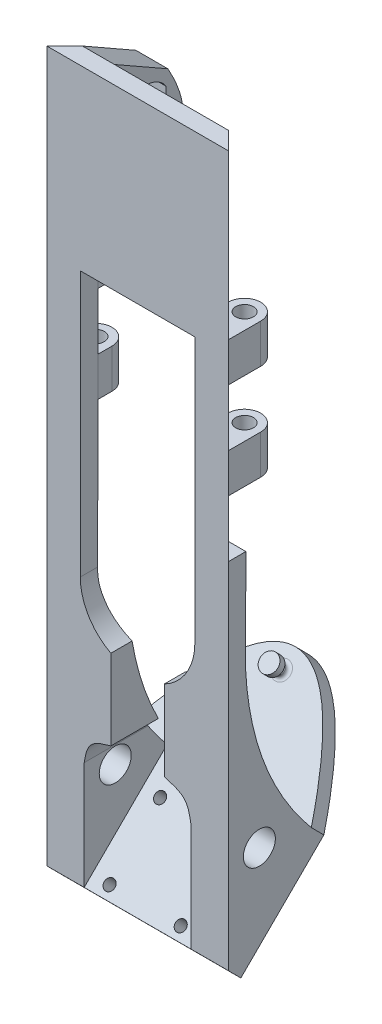
SolidWorks part; units mm, degrees
ref_plane "Front Plane" through (0, 0, 0) normal (0, 0, 1) x (1, 0, 0)
ref_plane "Top Plane" through (0, 0, 0) normal (0, 1, 0) x (1, 0, 0)
ref_plane "Right Plane" through (0, 0, 0) normal (1, 0, 0) x (0, 0, -1)
sketch "Sketch1" plane through (0, 0, 0) normal (0, 1, 0) x (1, 0, 0)
  line L0 (-25.5, 5) -> (-25.5, 9.1071)
  line L1 (25.5, 0) -> (-25.5, 0)
  line L2 (0, 0) -> (0, 5) construction
  line L3 (16.3088, 5) -> (-16.3088, 5)
  line L4 (-25.5, 0) -> (-25.5, 5)
  line L5 (-16.3088, 9.1071) -> (-16.3088, 5)
  line L6 (-16.3088, 5) -> (-25.5, 5) construction
  line L7 (16.3088, 9.1071) -> (16.3088, 5)
  line L8 (25.5, 5) -> (25.5, 9.1071)
  line L9 (25.5, 0) -> (25.5, 5)
  circle A1 centre (-20.9604, 9.1071) radius 2.5
  arc A3 (-25.5, 9.1071) -> (-16.3088, 9.1071) centre (-20.9044, 9.1071) cw
  circle A4 centre (20.9604, 9.1071) radius 2.5
  arc A5 (25.5, 9.1071) -> (16.3088, 9.1071) centre (20.9044, 9.1071) ccw
  dimension "D2" = 5
  dimension "D3" = 5
  dimension "D4" = 4.5956
  dimension "D1" = 25.5
extrude "Boss-Extrude1" add sketch "Sketch1" along normal blind 200
sketch "Sketch4" plane through (25.5, 0, 0) normal (1, 0, 0) x (0, 0, -1)
  line L1 (5, 170) -> (13.7027, 170)
  line L2 (5, 170) -> (5, 154)
  line L3 (5, 154) -> (13.7027, 154)
  line L4 (13.7027, 170) -> (13.7027, 154)
  line L5 (0, 200) -> (0, 0) construction
  line L6 (13.7027, 0) -> (13.7027, 200) construction
  line L15 (5, 143) -> (13.7027, 143)
  line L16 (5, 143) -> (5, 127)
  line L17 (5, 127) -> (13.7027, 127)
  line L18 (13.7027, 143) -> (13.7027, 127)
  line L19 (5, 116) -> (13.7027, 116)
  line L23 (5, 100) -> (13.7027, 100) [skipped]
  line L24 (13.7027, 116) -> (13.7027, 100) [skipped]
  line L25 (5, 116) -> (5, 100) [skipped]
  line L26 (5, 116) -> (4.5536, 0)
  line L27 (0, 0) -> (9.1071, 0) construction
  line L28 (4.5536, 0) -> (13.7027, 0)
  line L29 (9.1071, 0) -> (13.7027, 0) construction
  line L30 (13.7027, 0) -> (13.7027, 116)
  line L31 (5, 170) -> (5, 200)
  line L32 (0, 200) -> (9.1071, 200) construction
  line L33 (5, 200) -> (13.7027, 200)
  line L34 (13.7027, 170) -> (13.7027, 200)
  line M4 (0, 0) -> (9.1071, 0)
  line M5 (9.1071, 0) -> (9.1071, 200)
  line M6 (9.1071, 200) -> (0, 200)
  dimension "D1" = 16
  dimension "D2" = 5
  dimension "D4" = 116
  dimension "D5" = 11
  dimension "D6" = 11
  dimension "D3" = 3
extrude "Cut-Extrude4" cut sketch "Sketch4" against normal through all contours L1 L34 L33 M5 | L31 L1 M5 M6 | L2 L3 L1 M5 | L4 L1 L3 M5 | L16 L17 L15 M5 | L18 L15 L17 M5 | L19 L26 M4 M5 | L28 L30 L19 M5 region at (25.5, 185, -7.0536) region at (25.5, 162, -7.0536) region at (25.5, 108, -11.4049) region at (25.5, 108, -7.0536) region at (25.5, 135, -11.4049) region at (25.5, 135, -7.0536) region at (25.5, 185, -11.4049) region at (25.5, 162, -11.4049) region at (25.5, 49.3279, -6.923) region at (25.5, 50, -11.4049)
chamfer "Chamfer2" distance 5 angle 45 1 edges at (0, 0, -4.5536) first distance on face at (0, 77.3333, -4.8512)
sketch "Sketch7" plane through (-25.5, 0, 0) normal (-1, 0, 0) x (0, 0, 1)
  line L0 (-4.5728, 5) -> (-23.3302, 23.6135)
  line L2 (-5, 116) -> (-4.5728, 5) construction
  line L3 (-4.83, 71.8196) -> (-4.5728, 5)
  line L5 (-4.5728, 5) -> (0, 0.4622) construction
  spline S0 degree 2 poles (-23.3302, 23.6135) (-6.1606, 44.077) (-4.83, 71.8196) knots 0 0 0 1 1 1
extrude "Boss-Extrude2" add sketch "Sketch7" against normal through all
sketch "Sketch5" plane through (0, 0, 0) normal (0, 0, 1) x (1, 0, 0)
  line L0 (-16.0968, 75.4622) -> (-16.0968, 150)
  line L1 (-15, 38.66) -> (-7.5, 38.66) construction
  line L2 (-15, 30.832) -> (-15, 0)
  line L3 (-15, 0) -> (15, 0)
  line L4 (15, 30.832) -> (15, 0)
  line L6 (-25.5, 0.4622) -> (25.5, 0.4622) construction
  line L7 (-7.5, 75.4622) -> (7.5, 75.4622)
  line L8 (-7.5, 75.4622) -> (-7.5, 38.66)
  line L9 (-7.5, 38.66) -> (7.5, 38.66) construction
  line L10 (7.5, 75.4622) -> (7.5, 38.66)
  line L11 (-16.0968, 150) -> (16.0968, 150)
  line L12 (16.0968, 150) -> (16.0968, 75.4622)
  line L13 (-7.5, 38.66) -> (7.5, 38.66) construction
  line L14 (7.5, 38.66) -> (15, 38.66) construction
  line L15 (-15, 38.66) -> (-15, 30.832) construction
  line L16 (0, 0) -> (0, 83.4591) construction
  line L17 (15, 38.66) -> (15, 30.832) construction
  line L18 (-25.5, 200) -> (25.5, 200) construction
  circle A0 centre (0, 75.4622) radius 16.0968
  spline S0 degree 3 poles (-7.5, 38.66) (-9.7956, 38.0172) (-13.9471, 36.8549) (-14.6747, 32.6926) (-15, 30.832) knots 0 0 0 0 0.552974 1 1 1 1
  spline S1 degree 3 poles (7.5, 38.66) (9.7956, 38.0172) (13.9471, 36.8549) (14.6747, 32.6926) (15, 30.832) knots 0 0 0 0 0.552974 1 1 1 1
  point P4 (0, 0)
  line M7 (-25.5, 0.4622) -> (25.5, 0.4622)
  line M9 (25.5, 200) -> (-25.5, 200)
  dimension "D1" = 30
  dimension "D2" = 15
  dimension "D3" = 75
  dimension "D4" = 50
extrude "Cut-Extrude5" cut sketch "Sketch5" against normal through all contours L10 A0 L8 L7 | L8 A0 L10 L7 | A0 L8 L1 L10 | L4 L1 L2 M7 | A0 L12 L0 M9 region at (0, 118.9481, 0) region at (0, 78.5617, 0) region at (0, 25.8407, 0) region at (0, 67.7056, 0)
sketch "Sketch8" plane through (-25.5, 0, 0) normal (-1, 0, 0) x (0, 0, 1)
  line L1 (-23.3302, 23.6135) -> (0, 0.4622) construction
  circle A0 centre (-8.7271, 26.028) radius 4.5
  dimension "D1" = 9
  dimension "D2" = 12
extrude "Cut-Extrude6" cut sketch "Sketch8" against normal through all
sketch "Sketch9" plane through (0, 0.2329, 0.2311) normal (0, -0.7098, -0.7044) x (1, 0, 0)
  line L0 (-25.5, -0.3256) -> (-25.5, -33.1931)
  line L1 (-25.5, -0.3256) -> (25.5, -0.3256)
  line L5 (25.5, -0.3256) -> (25.5, -33.1931)
  spline S0 degree 2 poles (-25.5, -33.1931) (0, -92.2955) (25.5, -33.1931) knots 0 0 0 1 1 1
extrude "Boss-Extrude3" add sketch "Sketch9" along normal blind 5
sketch "Sketch10" plane through (0, 0.2329, 0.2311) normal (0, 0.7098, 0.7044) x (1, 0, 0)
  line L0 (0, 57.3395) -> (0, -1.5639) construction
  line L1 (0, 33.1931) -> (25.5, 33.1931) construction
  line L2 (-15, 33.1931) -> (-25.5, 33.1931) construction
  line L3 (-7.334, 27.3395) -> (0, 27.3395) construction
  line L4 (0, 27.3395) -> (10.7318, 27.3395) construction
  line L5 (-25.5, 33.1931) -> (0, 33.1931) construction
  circle A0 centre (0, 57.3395) radius 1.5
  parabola Q0 (-25.5, 33.1931) -> (25.5, 33.1931) focus (0, 57.2433) apex (0, 62.7443) construction
  dimension "D1" = 3
  dimension "D2" = 30
  dimension "D3" = 57.3395
extrude "Boss-Extrude4" add sketch "Sketch10" along normal blind 16 from offset 13 offset against normal yes
chamfer "Chamfer11" distance 5 angle 45 4 edges at (25.5, 135, -5) (25.5, 177, -5) (-25.5, 135, -5) (-25.5, 177, -5)
sketch "Sketch11" plane through (0, 2.3624, 2.3442) normal (0, 0.7098, 0.7044) x (1, 0, 0)
  circle A2 centre (0, 57.3395) radius 2.5
  circle A3 centre (0, 57.3395) radius 2.5
  dimension "D1" = 1
extrude "Boss-Extrude5" add sketch "Sketch11" along normal blind 2
fillet "Fillet1" radius 1 2 edges at (0, 39.5651, -39.405) (0, 41.6946, -37.2919)
sketch "Sketch13" plane through (-25.5, 0, 0) normal (-1, 0, 0) x (0, 0, 1)
  line L0 (-5, 200) -> (-5, 171)
  line L1 (-5, 154) -> (-5, 200) construction
  line L2 (-20.0185, 191.4487) -> (-5, 200)
  line L3 (-19.5, 187.4641) -> (-19.5, 180.5359)
  line L4 (-19.5, 187.4641) -> (-19.5, 180.5359) construction
  line L5 (-8.5, 187.4641) -> (-8.5, 180.5359)
  arc A0 (-8.5, 187.4641) -> (-19.5, 187.4641) centre (-14, 184) ccw
  arc A1 (-8.5, 180.5359) -> (-8.5, 187.4641) centre (-14, 184) ccw construction
  arc A2 (-19.5, 187.4641) -> (-19.5, 180.5359) centre (-14, 184) ccw construction
  arc A3 (-19.5, 180.5359) -> (-8.5, 180.5359) centre (-14, 184) ccw
  parabola Q0 (-5, 170.9991) -> (-20.0185, 191.4487) focus (-20.4582, 176.5502) apex (-23.168, 174.7999) construction
  spline S0 degree 2 poles (-5, 171) (-33.2542, 167.518) (-20.0185, 191.4487) knots 0 0 0 1 1 1
  dimension "D1" = 29
  dimension "D3" = 9
  dimension "D4" = 16
extrude "Boss-Extrude6" add sketch "Sketch13" against normal blind 9 from offset 5 contours L0 A0 region at (-25.5, 185.5, -5.3517) offset against normal yes
sketch "Sketch14" plane through (0, -3.3162, -3.2908) normal (0, -0.7098, -0.7044) x (1, 0, 0)
  line L0 (25.5, -0.3256) -> (-25.5, -0.3256) construction
  line L1 (0, 60.8431) -> (0, -60.8431) construction
  circle A0 centre (-10, -3.3256) radius 1.5
  circle A1 centre (-10, -23.3256) radius 1.5
  circle A2 centre (10, -23.3256) radius 1.5
  circle A3 centre (10, -3.3256) radius 1.5
  point P11 (0, 0)
  dimension "D1" = 3
  dimension "D2" = 3
  dimension "D3" = 20
  dimension "D4" = 3
  dimension "D5" = 10
extrude "Cut-Extrude7" cut sketch "Sketch14" against normal blind 10
sketch "Sketch15" plane through (0, 200, 0) normal (0, 1, 0) x (1, 0, 0)
  line L0 (25.5, 0) -> (20.5, 5)
  line L1 (20.5, 5) -> (25.5, 5)
  line L2 (25.5, 5) -> (25.5, 0)
  line L3 (-20.5, 5) -> (-25.5, 0)
  line L4 (-20.5, 5) -> (-25.5, 5)
  line L6 (-25.5, 5) -> (-25.5, 0)
extrude "Cut-Extrude8" cut sketch "Sketch15" against normal blind 16 from surface starting at face at (20.9604, 116, -11.6071)
